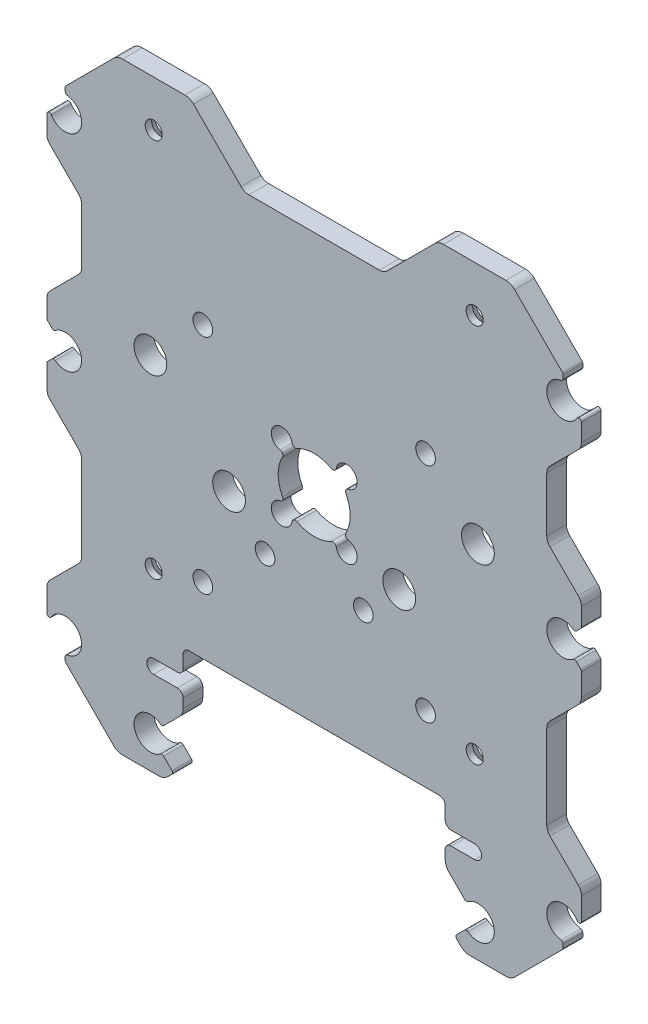
SolidWorks part; units mm, degrees
ref_plane "Front Plane" through (0, 0, 0) normal (0, 0, 1) x (1, 0, 0)
ref_plane "Top Plane" through (0, 0, 0) normal (0, 1, 0) x (1, 0, 0)
ref_plane "Right Plane" through (0, 0, 0) normal (1, 0, 0) x (0, 0, -1)
ref_plane "Plane1" through (0, 0, 3) normal (0, 0, 1) x (1, 0, 0)
sketch "Sketch1" plane through (0, 0, 3) normal (0, 0, 1) x (1, 0, 0)
  line L0 (252.3824, 372.8901) -> (252.3824, 373.9257)
  line L1 (252.3824, 373.9257) -> (244.4279, 381.8801)
  line L2 (244.4279, 381.8801) -> (184.3369, 381.8801)
  line L3 (184.3369, 381.8801) -> (176.3824, 373.9257)
  line L4 (176.3824, 373.9257) -> (176.3824, 372.8901)
  line L5 (173.5824, 368.8982) -> (173.5824, 302.8621)
  line L6 (176.3824, 298.8701) -> (176.3824, 297.8346)
  line L7 (176.3824, 297.8346) -> (184.3369, 289.8801)
  line L8 (184.3369, 289.8801) -> (244.4279, 289.8801)
  line L9 (244.4279, 289.8801) -> (252.3824, 297.8346)
  line L10 (252.3824, 297.8346) -> (252.3824, 298.8701)
  line L11 (255.1824, 302.8621) -> (255.1824, 368.8982)
  arc A0 (255.1824, 368.8982) -> (254.5153, 369.086) centre (254.8224, 368.8982) ccw
  arc A1 (254.5153, 369.086) -> (252.3824, 372.8901) centre (252.3824, 370.3901) ccw
  arc A2 (176.3824, 372.8901) -> (174.2495, 369.086) centre (176.3824, 370.3901) cw
  arc A3 (174.2495, 369.086) -> (173.5824, 368.8982) centre (173.9424, 368.8982) ccw
  arc A4 (173.5824, 302.8621) -> (174.2495, 302.6743) centre (173.9424, 302.8621) ccw
  arc A5 (174.2495, 302.6743) -> (176.3824, 298.8701) centre (176.3824, 301.3701) ccw
  arc A6 (252.3824, 298.8701) -> (254.5153, 302.6743) centre (252.3824, 301.3701) cw
  arc A7 (254.5153, 302.6743) -> (255.1824, 302.8621) centre (254.8224, 302.8621) ccw
extrude "Boss-Extrude1" add sketch "Sketch1" against normal blind 3
sketch "Sketch2" plane through (0, 0, 0) normal (0, 0, -1) x (-1, 0, 0)
  line L0 (-203.7279, 381.8801) -> (-225.0369, 381.8801)
  line L1 (-225.0369, 381.8801) -> (-225.0369, 373.5801)
  line L2 (-225.0369, 373.5801) -> (-203.7279, 373.5801)
  line L3 (-203.7279, 373.5801) -> (-203.7279, 381.8801)
extrude "Cut-Extrude1" cut sketch "Sketch2" against normal through all
sketch "Sketch3" plane through (0, 0, 0) normal (0, 0, -1) x (-1, 0, 0)
  line L0 (-173.5824, 350.5216) -> (-173.5824, 360.2158)
  line L1 (-173.5824, 360.2158) -> (-178.8824, 360.2158)
  line L2 (-178.8824, 360.2158) -> (-178.8824, 350.5216)
  line L3 (-178.8824, 350.5216) -> (-173.5824, 350.5216)
extrude "Cut-Extrude2" cut sketch "Sketch3" against normal through all
sketch "Sketch4" plane through (0, 0, 0) normal (0, 0, -1) x (-1, 0, 0)
  line L0 (-173.5824, 336.0901) -> (-173.5824, 341.6901)
  line L1 (-173.5824, 341.6901) -> (-179.1824, 336.0901)
  line L2 (-179.1824, 336.0901) -> (-173.5824, 336.0901)
extrude "Cut-Extrude3" cut sketch "Sketch4" against normal through all
sketch "Sketch5" plane through (0, 0, 0) normal (0, 0, -1) x (-1, 0, 0)
  line L0 (-173.5824, 306.997) -> (-173.5824, 331.8062)
  line L1 (-173.5824, 331.8062) -> (-178.8824, 331.8062)
  line L2 (-178.8824, 331.8062) -> (-178.8824, 306.997)
  line L3 (-178.8824, 306.997) -> (-173.5824, 306.997)
extrude "Cut-Extrude4" cut sketch "Sketch5" against normal through all
sketch "Sketch6" plane through (0, 0, 0) normal (0, 0, -1) x (-1, 0, 0)
  line L0 (-237.3113, 289.8801) -> (-191.4535, 289.8801)
  line L1 (-191.4535, 289.8801) -> (-192.9179, 291.3446)
  line L2 (-192.9179, 291.3446) -> (-184.3824, 299.8801)
  line L3 (-184.3824, 299.8801) -> (-194.3824, 299.8801)
  line L4 (-194.3824, 299.8801) -> (-194.3824, 308.7294)
  line L5 (-194.3824, 308.7294) -> (-234.3824, 308.7294)
  line L6 (-234.3824, 308.7294) -> (-234.3824, 299.8801)
  line L7 (-234.3824, 299.8801) -> (-244.3824, 299.8801)
  line L8 (-244.3824, 299.8801) -> (-235.8469, 291.3446)
  line L9 (-235.8469, 291.3446) -> (-237.3113, 289.8801)
extrude "Cut-Extrude5" cut sketch "Sketch6" against normal through all
sketch "Sketch7" plane through (0, 0, 0) normal (0, 0, -1) x (-1, 0, 0)
  line L0 (-194.3824, 305.0201) -> (-194.3824, 302.9201)
  line L1 (-194.3824, 302.9201) -> (-189.8824, 302.9201)
  line L2 (-189.8824, 305.0201) -> (-194.3824, 305.0201)
  arc A0 (-189.8824, 302.9201) -> (-189.8824, 305.0201) centre (-189.8824, 303.9701) ccw
extrude "Cut-Extrude6" cut sketch "Sketch7" against normal through all
sketch "Sketch8" plane through (0, 0, 0) normal (0, 0, -1) x (-1, 0, 0)
  line L0 (-234.3824, 302.9201) -> (-234.3824, 305.0201)
  line L1 (-234.3824, 305.0201) -> (-238.8824, 305.0201)
  line L2 (-238.8824, 302.9201) -> (-234.3824, 302.9201)
  arc A0 (-238.8824, 305.0201) -> (-238.8824, 302.9201) centre (-238.8824, 303.9701) ccw
extrude "Cut-Extrude7" cut sketch "Sketch8" against normal through all
sketch "Sketch9" plane through (0, 0, 0) normal (0, 0, -1) x (-1, 0, 0)
  line L0 (-255.1824, 326.5062) -> (-255.1824, 312.297)
  line L1 (-255.1824, 312.297) -> (-249.8824, 312.297)
  line L2 (-249.8824, 312.297) -> (-249.8824, 326.5062)
  line L3 (-249.8824, 326.5062) -> (-255.1824, 326.5062)
extrude "Cut-Extrude8" cut sketch "Sketch9" against normal through all
sketch "Sketch10" plane through (0, 0, 0) normal (0, 0, -1) x (-1, 0, 0)
  line L0 (-255.1824, 341.6901) -> (-255.1824, 336.0901)
  line L1 (-255.1824, 336.0901) -> (-249.5824, 341.6901)
  line L2 (-249.5824, 341.6901) -> (-255.1824, 341.6901)
extrude "Cut-Extrude9" cut sketch "Sketch10" against normal through all
sketch "Sketch11" plane through (0, 0, 0) normal (0, 0, -1) x (-1, 0, 0)
  line L0 (-255.1824, 365.5158) -> (-255.1824, 345.2216)
  line L1 (-255.1824, 345.2216) -> (-249.8824, 345.2216)
  line L2 (-249.8824, 345.2216) -> (-249.8824, 365.5158)
  line L3 (-249.8824, 365.5158) -> (-255.1824, 365.5158)
extrude "Cut-Extrude10" cut sketch "Sketch11" against normal through all
sketch "Sketch12" plane through (0, 0, 0) normal (0, 0, -1) x (-1, 0, 0)
  arc A0 (-219.2105, 341.5095) -> (-219.2105, 336.2408) centre (-214.3824, 338.8751) ccw
  arc A1 (-219.2105, 336.2408) -> (-219.5738, 335.507) centre (-219.6494, 336.0013) cw
  arc A2 (-219.5738, 335.507) -> (-217.7505, 333.6837) centre (-219.3321, 333.9254) cw
  arc A3 (-217.7505, 333.6837) -> (-217.0168, 334.0471) centre (-217.2562, 333.6082) cw
  arc A4 (-217.0168, 334.0471) -> (-211.748, 334.0471) centre (-214.3824, 338.8751) ccw
  arc A5 (-211.748, 334.0471) -> (-211.0143, 333.6837) centre (-211.5086, 333.6082) cw
  arc A6 (-211.0143, 333.6837) -> (-209.191, 335.507) centre (-209.4327, 333.9254) cw
  arc A7 (-209.191, 335.507) -> (-209.5543, 336.2408) centre (-209.1154, 336.0013) cw
  arc A8 (-209.5543, 336.2408) -> (-209.5543, 341.5095) centre (-214.3824, 338.8751) ccw
  arc A9 (-209.5543, 341.5095) -> (-209.191, 342.2432) centre (-209.1154, 341.749) cw
  arc A10 (-209.191, 342.2432) -> (-211.0143, 344.0666) centre (-209.4327, 343.8249) cw
  arc A11 (-211.0143, 344.0666) -> (-211.748, 343.7032) centre (-211.5086, 344.1421) cw
  arc A12 (-211.748, 343.7032) -> (-217.0168, 343.7032) centre (-214.3824, 338.8751) ccw
  arc A13 (-217.0168, 343.7032) -> (-217.7505, 344.0666) centre (-217.2562, 344.1421) cw
  arc A14 (-217.7505, 344.0666) -> (-219.5738, 342.2432) centre (-219.3321, 343.8249) cw
  arc A15 (-219.5738, 342.2432) -> (-219.2105, 341.5095) centre (-219.6494, 341.749) cw
extrude "Cut-Extrude11" cut sketch "Sketch12" against normal through all
draft "Draft1" type of draft neutral plane draft angle 45 faces to draft 1 face at (252.5324, 365.5158, 1.5) neutral plane through (255.1824, 302.8621, 0) neutral plane normal (1, 0, 0) parameters "D1"=45
draft "Draft2" type of draft neutral plane draft angle 45 faces to draft 1 face at (239.3824, 299.8801, 1.5) neutral plane through (234.3824, 308.7294, 3) neutral plane normal (-1, 0, 0) parameters "D1"=45
draft "Draft3" type of draft neutral plane draft angle 45 faces to draft 1 face at (189.3824, 299.8801, 1.5) neutral plane through (194.3824, 299.8801, 3) neutral plane normal (1, 0, 0) parameters "D1"=45
draft "Draft4" type of draft neutral plane draft angle 45 faces to draft 1 face at (176.2324, 306.997, 1.5) neutral plane through (173.5824, 368.8982, 0) neutral plane normal (-1, 0, 0) parameters "D1"=45
draft "Draft5" type of draft neutral plane draft angle 45 faces to draft 2 face at (252.3824, 341.6901, 1.5) face at (252.5324, 345.2216, 1.5) neutral plane through (255.1824, 302.8621, 0) neutral plane normal (1, 0, 0) parameters "D1"=45
draft "Draft6" type of draft neutral plane draft angle 45 faces to draft 2 face at (252.5324, 312.297, 1.5) face at (252.5324, 326.5062, 1.5) neutral plane through (249.8824, 312.297, 3) neutral plane normal (1, 0, 0) parameters "D1"=45
draft "Draft7" type of draft neutral plane draft angle 45 faces to draft 2 face at (176.3824, 336.0901, 1.5) face at (176.2324, 331.8062, 1.5) neutral plane through (173.5824, 368.8982, 0) neutral plane normal (-1, 0, 0) parameters "D1"=45
draft "Draft8" type of draft neutral plane draft angle 45 faces to draft 2 face at (176.2324, 360.2158, 1.5) face at (176.2324, 350.5216, 1.5) neutral plane through (178.8824, 360.2158, 3) neutral plane normal (-1, 0, 0) parameters "D1"=45
draft "Draft9" type of draft neutral plane draft angle 45 faces to draft 2 face at (225.0369, 377.7301, 1.5) face at (203.7279, 377.7301, 1.5) neutral plane through (225.0369, 373.5801, 3) neutral plane normal (0, 1, 0) parameters "D1"=45
ref_plane "Plane2" through (0, 343.8249, 0) normal (0, 1, 0) x (1, 0, 0)
sketch "Sketch13" plane through (0, 343.8249, 0) normal (0, 1, 0) x (1, 0, 0)
  line L0 (211.0327, 0) -> (209.4327, 0)
  line L1 (209.4327, 0) -> (209.4327, -3)
  line L2 (209.4327, -3) -> (211.0327, -3)
  line L3 (211.0327, -3) -> (211.0327, 0)
  line L4 (209.4327, 0) -> (209.4327, -3) construction
revolve "Cut-Revolve1" cut sketch "Sketch13" angle 360 about L4 reverse direction yes
ref_plane "Plane3" through (0, 333.9254, 0) normal (0, 1, 0) x (1, 0, 0)
sketch "Sketch14" plane through (0, 333.9254, 0) normal (0, 1, 0) x (1, 0, 0)
  line L0 (211.0327, 0) -> (209.4327, 0)
  line L1 (209.4327, 0) -> (209.4327, -3)
  line L2 (209.4327, -3) -> (211.0327, -3)
  line L3 (211.0327, -3) -> (211.0327, 0)
  line L4 (209.4327, 0) -> (209.4327, -3) construction
revolve "Cut-Revolve2" cut sketch "Sketch14" angle 360 about L4 reverse direction yes
sketch "Sketch15" plane through (0, 333.9254, 0) normal (0, 1, 0) x (1, 0, 0)
  line L0 (220.9321, 0) -> (219.3321, 0)
  line L1 (219.3321, 0) -> (219.3321, -3)
  line L2 (219.3321, -3) -> (220.9321, -3)
  line L3 (220.9321, -3) -> (220.9321, 0)
  line L4 (219.3321, 0) -> (219.3321, -3) construction
revolve "Cut-Revolve3" cut sketch "Sketch15" angle 360 about L4 reverse direction yes
sketch "Sketch16" plane through (0, 343.8249, 0) normal (0, 1, 0) x (1, 0, 0)
  line L0 (220.9321, 0) -> (219.3321, 0)
  line L1 (219.3321, 0) -> (219.3321, -3)
  line L2 (219.3321, -3) -> (220.9321, -3)
  line L3 (220.9321, -3) -> (220.9321, 0)
  line L4 (219.3321, 0) -> (219.3321, -3) construction
revolve "Cut-Revolve4" cut sketch "Sketch16" angle 360 about L4 reverse direction yes
ref_plane "Plane4" through (0, 370.3901, 0) normal (0, 1, 0) x (1, 0, 0)
sketch "Sketch17" plane through (0, 370.3901, 0) normal (0, 1, 0) x (1, 0, 0)
  line L0 (254.8824, 0) -> (252.3824, 0)
  line L1 (252.3824, 0) -> (252.3824, -3)
  line L2 (252.3824, -3) -> (254.8824, -3)
  line L3 (254.8824, -3) -> (254.8824, 0)
  line L4 (252.3824, 0) -> (252.3824, -3) construction
revolve "Cut-Revolve5" cut sketch "Sketch17" angle 360 about L4 reverse direction yes
ref_plane "Plane5" through (0, 301.3701, 0) normal (0, 1, 0) x (1, 0, 0)
sketch "Sketch18" plane through (0, 301.3701, 0) normal (0, 1, 0) x (1, 0, 0)
  line L0 (178.8824, 0) -> (176.3824, 0)
  line L1 (176.3824, 0) -> (176.3824, -3)
  line L2 (176.3824, -3) -> (178.8824, -3)
  line L3 (178.8824, -3) -> (178.8824, 0)
  line L4 (176.3824, 0) -> (176.3824, -3) construction
revolve "Cut-Revolve6" cut sketch "Sketch18" angle 360 about L4 reverse direction yes
hole_wizard "CSK for M2 Flat Head Machine Screw1" positions "Sketch20" profile "Sketch19" countersink size "M2" standard "ANSI Metric"
sketch "Sketch20" plane through (0, 0, 0) normal (0, 0, -1) x (-1, 0, 0)
  point P0 (-238.8824, 316.8801)
  point P1 (-189.8824, 316.8801)
  point P2 (-189.8824, 374.8801)
  point P3 (-238.8824, 374.8801)
sketch "Sketch19" plane through (238.8824, 316.8801, 0) normal (1, 0, 0) x (0, 1, 0)
  line L0 (0, 0) -> (0, 3)
  line L1 (0, 3) -> (1.3, 3)
  line L2 (1.3, 3) -> (1.3, 2)
  line L3 (1.3, 2) -> (3.3, 0)
  line L5 (3.3, 0) -> (0, 0)
  line L6 (-1.3, 2) -> (-3.3, 0) construction
  line L11 (0, -6.35) -> (0, 107.95) construction
  dimension "Thru Hole Dia." = 2.6
  dimension "Thru Hole Depth" = 3
  dimension "Near C'Sink Dia." = 6.6
  dimension "Near C'Sink Angle" = 90
hole_wizard "Ø3.0 (3) Diameter Hole1" positions "Sketch22" profile "Sketch21" hole size "Ø3.0" standard "ANSI Metric"
sketch "Sketch22" plane through (0, 0, 3) normal (0, 0, 1) x (1, 0, 0)
  point P0 (206.8824, 327.3801)
  point P1 (221.8824, 327.3801)
  point P2 (197.3824, 352.8801)
  point P3 (231.3824, 318.8801)
  point P4 (231.3824, 352.8801)
  point P5 (197.3824, 318.8801)
sketch "Sketch21" plane through (206.8824, 327.3801, 3) normal (1, 0, 0) x (0, -1, 0)
  line L0 (0, 0) -> (0, 3)
  line L1 (0, 3) -> (1.5, 3)
  line L2 (1.5, 3) -> (1.5, 0)
  line L5 (1.5, 0) -> (0, 0)
  line L11 (0, -6.35) -> (0, 107.95) construction
  dimension "Thru Hole Dia." = 3
  dimension "Thru Hole Depth" = 3
hole_wizard "Ø5.0 (5) Diameter Hole1" positions "Sketch24" profile "Sketch23" hole size "Ø5.0" standard "ANSI Metric"
sketch "Sketch24" plane through (0, 0, 3) normal (0, 0, 1) x (1, 0, 0)
  point P0 (176.3824, 338.8901)
  point P1 (189.3824, 294.8801)
  point P2 (239.3824, 294.8801)
  point P3 (252.3824, 338.8901)
  point P4 (227.3724, 332.8701)
  point P5 (189.3824, 344.8801)
  point P6 (239.3824, 344.8801)
  point P7 (201.3924, 332.8701)
sketch "Sketch23" plane through (176.3824, 338.8901, 3) normal (1, 0, 0) x (0, -1, 0)
  line L0 (0, 0) -> (0, 3)
  line L1 (0, 3) -> (2.5, 3)
  line L2 (2.5, 3) -> (2.5, 0)
  line L5 (2.5, 0) -> (0, 0)
  line L11 (0, -6.35) -> (0, 107.95) construction
  dimension "Thru Hole Dia." = 5
  dimension "Thru Hole Depth" = 3
fillet "Fillet1" radius 0.36 22 edges at (176.3824, 298.8701, 1.5) (255.1824, 341.6901, 1.5) (252.3824, 298.8701, 1.5) (176.3824, 297.8346, 1.5) (191.1502, 296.6479, 1.5) (174.6146, 340.6579, 1.5) (252.3824, 297.8346, 1.5) (173.5824, 336.0901, 1.5) (176.3824, 372.8901, 1.5) (254.1502, 337.1224, 1.5) (174.6146, 337.1224, 1.5) (252.3824, 373.9257, 1.5) (255.1824, 336.0901, 1.5) (237.6146, 296.6479, 1.5) (254.1502, 340.6579, 1.5) (237.6146, 293.1124, 1.5) (176.3824, 373.9257, 1.5) (235.8469, 291.3446, 1.5) (173.5824, 341.6901, 1.5) (192.9179, 291.3446, 1.5) (252.3824, 372.8901, 1.5) (191.1502, 293.1124, 1.5) tangent propagation no
fillet "Fillet2" radius 0.89 6 edges at (194.3824, 308.7294, 1.5) (234.3824, 305.0201, 1.5) (234.3824, 308.7294, 1.5) (194.3824, 302.9201, 1.5) (194.3824, 305.0201, 1.5) (234.3824, 302.9201, 1.5) tangent propagation no
fillet "Fillet3" radius 1.69 18 edges at (249.8824, 350.5216, 1.5) (225.0369, 373.5801, 1.5) (178.8824, 360.2158, 1.5) (255.1824, 306.997, 1.5) (173.5824, 365.5158, 1.5) (249.8824, 326.5062, 1.5) (255.1824, 365.5158, 1.5) (255.1824, 345.2216, 1.5) (178.8824, 350.5216, 1.5) (173.5824, 306.997, 1.5) (203.7279, 373.5801, 1.5) (173.5824, 345.2216, 1.5) (249.8824, 312.297, 1.5) (173.5824, 331.8062, 1.5) (255.1824, 331.8062, 1.5) (178.8824, 326.5062, 1.5) (178.8824, 312.297, 1.5) (249.8824, 360.2158, 1.5) tangent propagation no
fillet "Fillet4" radius 1.89 10 edges at (191.4535, 289.8801, 1.5) (237.3113, 289.8801, 1.5) (234.3824, 299.8801, 1.5) (244.4279, 381.8801, 1.5) (184.3369, 289.8801, 1.5) (233.3369, 381.8801, 1.5) (194.3824, 299.8801, 1.5) (195.4279, 381.8801, 1.5) (184.3369, 381.8801, 1.5) (244.4279, 289.8801, 1.5) tangent propagation no
ref_axis "Axis1" through (252.3824, 370.3901, 0) along (0, 0, 1)
ref_axis "Axis2" through (176.3824, 370.3901, 0) along (0, 0, 1)
ref_axis "Axis3" through (176.3824, 338.8901, 0) along (0, 0, 1)
ref_axis "Axis4" through (176.3824, 301.3701, 0) along (0, 0, 1)
ref_axis "Axis5" through (252.3824, 301.3701, 0) along (0, 0, 1)
ref_axis "Axis6" through (239.3824, 294.8801, 0) along (0, 0, 1)
ref_axis "Axis7" through (189.3824, 294.8801, 0) along (0, 0, 1)
